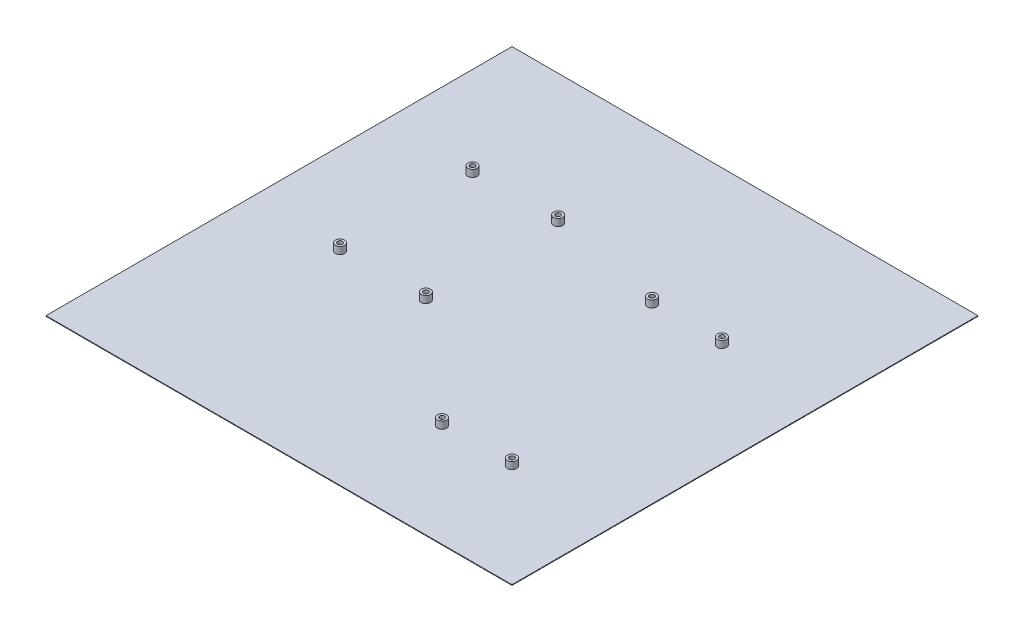
SolidWorks part; units mm, degrees
ref_plane "Front Plane" through (0, 0, 0) normal (0, 0, 1) x (1, 0, 0)
ref_plane "Top Plane" through (0, 0, 0) normal (0, 1, 0) x (1, 0, 0)
ref_plane "Right Plane" through (0, 0, 0) normal (1, 0, 0) x (0, 0, -1)
sketch "Sketch1" plane through (0, 0, 0) normal (0, 1, 0) x (1, 0, 0)
  line L1 (-166.5, -166.5) -> (166.5, -166.5)
  line L2 (-166.5, -166.5) -> (-166.5, 166.5)
  line L3 (-166.5, 166.5) -> (166.5, 166.5)
  line L4 (166.5, -166.5) -> (166.5, 166.5)
  line L5 (-166.5, -166.5) -> (166.5, 166.5) construction
  line L6 (-166.5, 166.5) -> (166.5, -166.5) construction
  point P0 (0, 0)
  dimension "D1" = 333
  dimension "D2" = 333
extrude "Boss-Extrude1" add sketch "Sketch1" along normal blind 0.45
sketch "Sketch6" plane through (0, 0.45, 0) normal (0, 1, 0) x (1, 0, 0)
  circle A0 centre (93, 57) radius 3.3
  circle A1 centre (43, 57) radius 3.3
  circle A2 centre (93, -93) radius 3.3
  circle A3 centre (43, -93) radius 3.3
sketch "Sketch7" plane through (0, 0.45, 0) normal (0, 1, 0) x (1, 0, 0)
  circle A0 centre (-101.9441, 73.7185) radius 3.3
  circle A1 centre (-40.9446, 73.9643) radius 3.3
  circle A2 centre (-40.5619, -21.035) radius 3.3
  circle A3 centre (-101.5614, -21.2807) radius 3.3
extrude "Boss-Extrude2" add sketch "Sketch7" along normal blind 5
sketch "Sketch8" plane through (0, 5.45, 0) normal (0, 1, 0) x (1, 0, 0)
  circle A0 centre (-40.5619, -21.035) radius 1.75
  circle A1 centre (-40.9446, 73.9643) radius 1.75
  circle A2 centre (-101.9441, 73.7185) radius 1.75
  circle A3 centre (-101.5614, -21.2807) radius 1.75
extrude "Cut-Extrude1" cut sketch "Sketch8" against normal blind 4
extrude "Boss-Extrude3" add sketch "Sketch6" along normal blind 5
sketch "Sketch10" plane through (0, 5.45, 0) normal (0, 1, 0) x (1, 0, 0)
  circle A0 centre (43, 57) radius 1.75
  circle A1 centre (93, 57) radius 1.75
  circle A2 centre (93, -93) radius 1.75
  circle A3 centre (43, -93) radius 1.75
extrude "Cut-Extrude2" cut sketch "Sketch10" against normal blind 4
